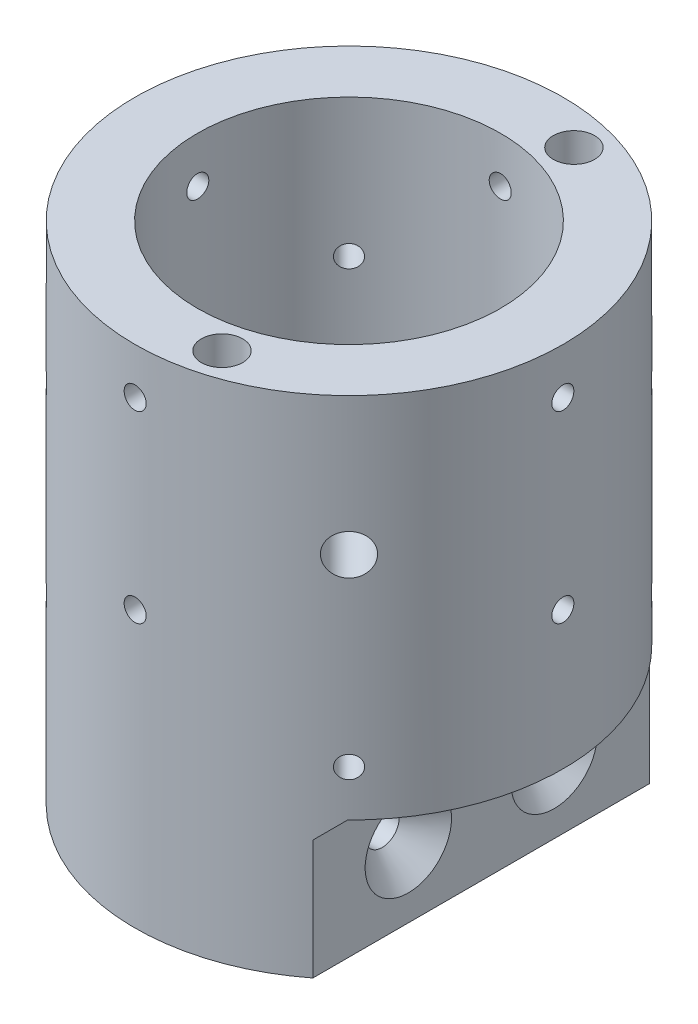
SolidWorks part; units mm, degrees
material "PLA плотность"
ref_plane "Спереди" through (0, 0, 0) normal (0, 0, 1) x (1, 0, 0)
ref_plane "Сверху" through (0, 0, 0) normal (0, 1, 0) x (1, 0, 0)
ref_plane "Справа" through (0, 0, 0) normal (1, 0, 0) x (0, 0, -1)
sketch "Эскиз1" plane through (0, 0, 0) normal (0, 1, 0) x (1, 0, 0)
  circle A0 centre (0, 0) radius 23.3
  dimension "D1" = 46.6
extrude "Бобышка-Вытянуть1" add sketch "Эскиз1" along normal blind 5
sketch "Эскиз2" plane through (0, 5, 0) normal (0, 1, 0) x (1, 0, 0)
  circle A0 centre (0, 0) radius 23.3
  circle A1 centre (0, 0) radius 16.5
  circle A2 centre (0, 0) radius 23.3 construction
  dimension "D1" = 33
  dimension "D2" = 0
extrude "Бобышка-Вытянуть2" add sketch "Эскиз2" along normal blind 35
chamfer "Фаска8" distance 2 angle 45 1 edges at (0, 5, 16.5)
sketch "Эскиз3" plane through (0, 0, 0) normal (1, 0, 0) x (0, 0, -1)
  line L0 (-23.3, 20) -> (28.0263, 20) construction
  line L1 (-23.3, 40) -> (-23.3, 0) construction
  line L2 (16.5, 40) -> (-16.5, 40) construction
  circle A1 centre (0, 35) radius 1.2
  dimension "D1" = 2.4
  dimension "D2" = 5
extrude "Вырез-Вытянуть1" cut sketch "Эскиз3" against normal through all
ref_plane "Плоскость1" through (0, 0, 0) normal (0.7071, 0, 0.7071) x (0, -1, 0)
sketch "Эскиз4" plane through (0, 0, 0) normal (0.7071, 0, 0.7071) x (0, -1, 0)
  line L0 (-20, 23.3) -> (-20, -30.0625) construction
  line L1 (0, 23.3) -> (-40, 23.3) construction
  line L3 (0, -23.3) -> (0, 23.3) construction
  circle A1 centre (-5, 0) radius 1.2
  dimension "D1" = 5
  dimension "D2" = 2.4
extrude "Вырез-Вытянуть2" cut sketch "Эскиз4" against normal through all from offset 16.3 offset against normal yes
pattern_circular "Круговой массив1" count 4 over 360 about axis through (0, 5, 0) along (0, -1, 0) of "Вырез-Вытянуть2"
pattern_circular "Круговой массив2" count 4 over 360 about axis through (0, 5, 0) along (0, -1, 0) of "Вырез-Вытянуть1"
pattern_linear "Линейный массив3" count 2 spacing 20 along (0, 1, 0) of "Круговой массив1"
pattern_linear "Линейный массив4" count 2 spacing 20 along (0, -1, 0) of "Круговой массив2"
sketch "Эскиз12" plane through (0, 0, 0) normal (0, -1, 0) x (1, 0, 0)
  line L1 (14.3923, 18.3235) -> (14.3923, -18.3235)
  line L20 (0, 15) -> (-2.7835, 17.7835)
  line L21 (-2.7835, -17.7835) -> (0, -15)
  line L22 (0, -15) -> (0, 15)
  line L23 (0, 15) -> (-2.7835, 17.7835)
  line L24 (-2.7835, -17.7835) -> (0, -15)
  line L25 (0, -15) -> (0, 15)
  circle A6 centre (0, 0) radius 23.3 construction
  arc A7 (14.3923, 18.3235) -> (14.3923, -18.3235) centre (0, 0) ccw
  arc A13 (-2.7835, 17.7835) -> (-2.7835, -17.7835) centre (0, 0) ccw
  arc A14 (-2.7835, 17.7835) -> (-2.7835, -17.7835) centre (0, 0) ccw
  dimension "D1" = 0
extrude "Бобышка-Вытянуть3" add sketch "Эскиз12" along normal blind 15 contours L1 region at (13.7929, 0, 0)
sketch "Эскиз13" plane through (0, -15, 0) normal (0, -1, 0) x (1, 0, 0)
  line L14 (-2.6786, -18.1029) -> (0.3, -15.1243)
  line L15 (0.3, 15.1243) -> (-2.6786, 18.1029)
  line L16 (0.3, -15.1243) -> (0.3, 15.1243)
  line L17 (-2.6786, -18.1029) -> (0.3, -15.1243)
  line L18 (0.3, 15.1243) -> (-2.6786, 18.1029)
  line L19 (0.3, -15.1243) -> (0.3, 15.1243)
  arc A5 (-2.6786, 18.1029) -> (-2.6786, -18.1029) centre (0, 0) ccw
  arc A6 (-2.6786, 18.1029) -> (-2.6786, -18.1029) centre (0, 0) ccw
  dimension "D1" = 0.3
extrude "Вырез-Вытянуть10" cut sketch "Эскиз13" against normal up to surface (15 mm away) up to face at (18.8461, 0, 0)
chamfer "Фаска4" distance 2 angle 45 1 edges at (14.3923, 0, 0)
chamfer "Фаска6" distance 2 angle 45 4 edges at (-1.1893, 0, -16.6136) (-18.3, 0, 0) (0.3, 0, 0) (-1.1893, 0, 16.6136)
chamfer "Фаска7" distance 2 angle 45 4 edges at (-1.1893, -15, -16.6136) (-18.3, -15, 0) (-1.1893, -15, 16.6136) (0.3, -15, 0)
sketch "Эскиз17" plane through (0, -15, 0) normal (0, -1, 0) x (1, 0, 0)
  circle A0 centre (5.3288, 0) radius 2.5
extrude "Вырез-Вытянуть11" cut sketch "Эскиз17" against normal blind 86
ref_plane "Плоскость2" through (0, 0, 0) normal (-0.7071, 0, -0.7071) x (-0.7071, 0, 0.7071)
sketch "Эскиз18" plane through (0, 0, 0) normal (-0.7071, 0, -0.7071) x (-0.7071, 0, 0.7071)
  circle A0 centre (0, 25) radius 1.2 construction
  circle A1 centre (0, 25) radius 1.2
  circle A2 centre (0, 25) radius 2.2
extrude "Вырез-Вытянуть12" cut sketch "Эскиз18" against normal blind 86
sketch "Эскиз21" plane through (0, -15, 0) normal (0, -1, 0) x (1, 0, 0)
  line L0 (5.3288, -15.6158) -> (5.3288, -22.6825) construction
  circle A0 centre (5.3288, -19.1491) radius 2.25
  circle A1 centre (0, 0) radius 16.5 construction
  circle A2 centre (0, 0) radius 16.5 construction
  arc A3 (14.3923, 18.3235) -> (14.3923, -18.3235) centre (0, 0) ccw construction
  dimension "D1" = 4.5
extrude "Вырез-Вытянуть13" cut sketch "Эскиз21" against normal through all
mirror "Зеркальное отражение1" about plane through (0, 0, 0) normal (0, 0, 1) of "Вырез-Вытянуть13"
hole_wizard "Зенковка для винта с полупотайной головкой M41" positions "Эскиз22" profile "Эскиз23" countersink size "M4" standard "ISO" end condition through all
sketch "Эскиз22" plane through (14.3923, -676.2045, -24.0267) normal (1, 0, 0) x (0, -0.1282, -0.9918)
  line L0 (-110.237, 665.565) -> (-108.5708, 652.6722) construction
  line L4 (-109.4039, 659.1186) -> (-20.4413, 659.1186) construction
  line L5 (-20.4413, 659.1186) -> (-1.8045, 659.1186) construction
  point P0 (-117.4039, 659.1186)
  point P19 (-101.6667, 661.1523)
sketch "Эскиз23" plane through (14.3923, -7.4747, 7.934) normal (0, 1, 0) x (0, 0, -1)
  line L0 (0, 0) -> (0, 37.6923)
  line L1 (0, 37.6923) -> (1.85, 37.6923)
  line L2 (1.85, 37.6923) -> (1.85, 2.85)
  line L3 (1.85, 2.85) -> (4.7, 0)
  line L4 (4.7, 0) -> (0, 0)
  line L5 (-1.85, 2.85) -> (-4.7, 0) construction
  line L6 (0, -6.35) -> (0, 107.95) construction
  dimension "Диаметр сквозного отверстия" = 3.7
  dimension "Глубина сквозного отверстия" = 37.6923
  dimension "Диаметр передней зенковки" = 9.4
  dimension "Угол передней зенковки" = 90
